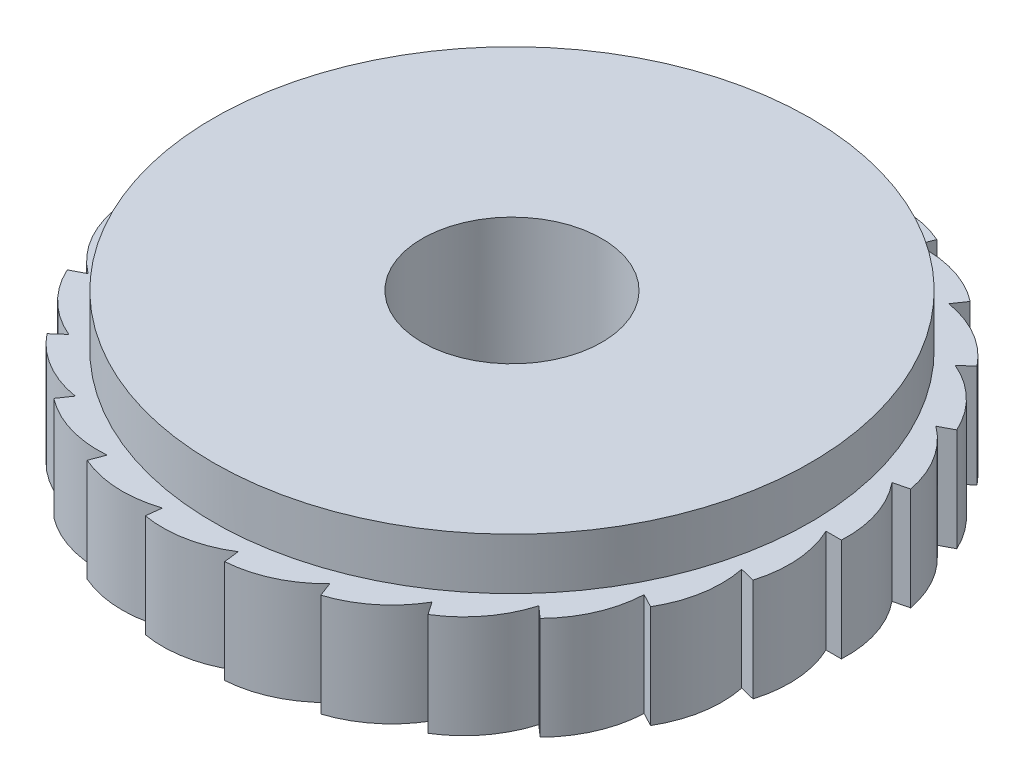
SolidWorks part; units mm, degrees
ref_plane "Front Plane" through (0, 0, 0) normal (0, 0, 1) x (1, 0, 0)
ref_plane "Top Plane" through (0, 0, 0) normal (0, 1, 0) x (1, 0, 0)
ref_plane "Right Plane" through (0, 0, 0) normal (1, 0, 0) x (0, 0, -1)
sketch "Sketch1" plane through (0, 0, 0) normal (0, 1, 0) x (1, 0, 0)
  line L0 (0, 0) -> (54.8903, 0) construction
  line L1 (0, 0) -> (47.5263, 11.7142) construction
  line L2 (0, 0) -> (29.6137, 7.2991)
  line L3 (0, 0) -> (32, 0)
  circle A0 centre (0, 0) radius 32 construction
  circle A1 centre (0, 0) radius 30.5 construction
  arc A2 (29.6137, 7.2991) -> (32, 0) centre (21.3514, 0.5583) cw
  circle A3 centre (0, 0) radius 31.25 construction
  dimension "D1" = 62.5
  dimension "D2" = 1.5
  dimension "D4" = 0.75
  dimension "D3" = 13.846
extrude "Extrude ratchet edge" add sketch "Sketch1" along normal blind 10
pattern_circular "Pattern edge to form gear" count 26 over 360 about axis through (0, 10, 0) along (0, -1, 0) of "Extrude ratchet edge" reverse direction yes
sketch "Iteration wheel" plane through (0, 10, 0) normal (0, 1, 0) x (1, 0, 0)
  circle A0 centre (0, 0) radius 29
  dimension "D1" = 58
extrude "Extrude iteration wheel" add sketch "Iteration wheel" along normal blind 5
sketch "Sketch7" plane through (0, 15, 0) normal (0, 1, 0) x (1, 0, 0)
  circle A0 centre (0, 0) radius 8.7313
  dimension "D1" = 17.4625
extrude "Cut-Extrude2" cut sketch "Sketch7" against normal through all contours A0
equation "\"Bearing size\"= 17.4625mm"
equation "\"D1@Sketch7\" = \"Bearing size\""
